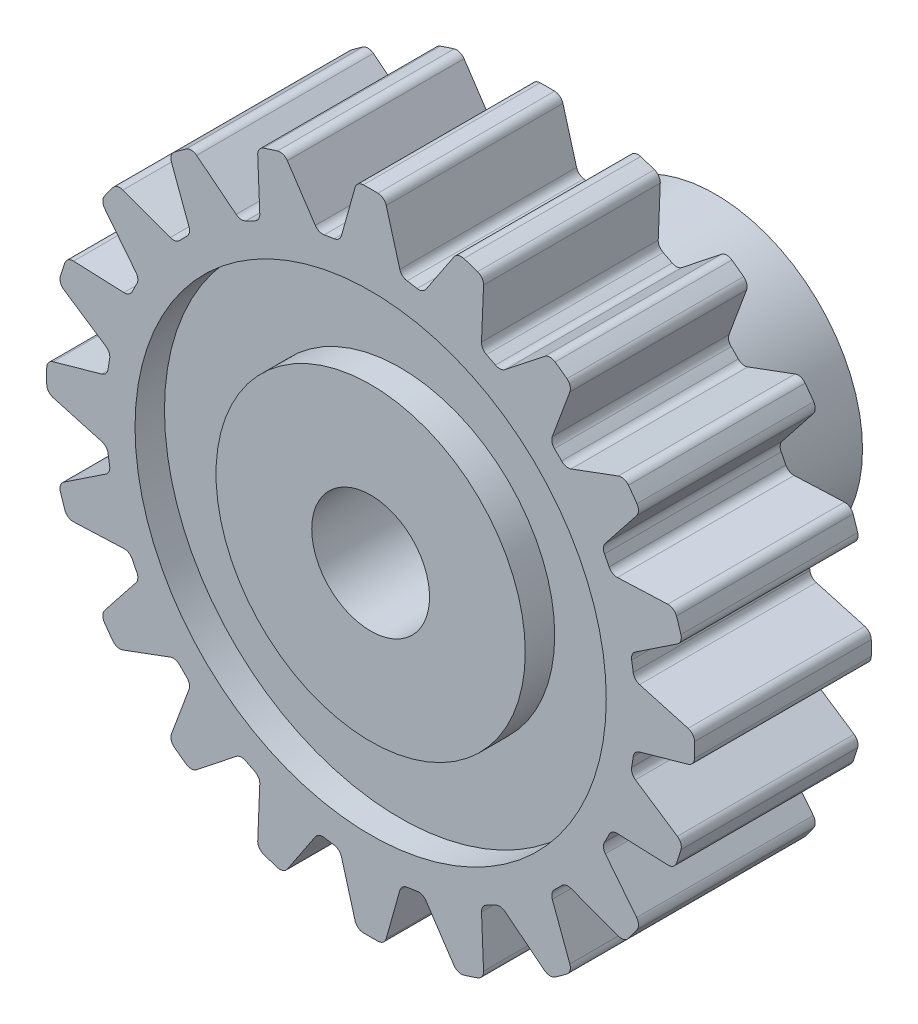
SolidWorks part; units mm, degrees
ref_plane "Front Plane" through (0, 0, 0) normal (0, 0, 1) x (1, 0, 0)
ref_plane "Top Plane" through (0, 0, 0) normal (0, 1, 0) x (1, 0, 0)
ref_plane "Right Plane" through (0, 0, 0) normal (1, 0, 0) x (0, 0, -1)
sketch "Sketch1" plane through (0, 0, 0) normal (0, 0, 1) x (1, 0, 0)
  circle A2 centre (0, 0) radius 9
  dimension "Blank diameter" = 18
extrude "Body" add sketch "Sketch1" against normal blind 6
sketch "Sketch2" plane through (0, 0, 0) normal (0, 0, 1) x (1, 0, 0)
  line L0 (0, 16.3446) -> (0, 3.6554) construction
  line L1 (-0.755, 9.9715) -> (-1.0446, 8.9392)
  line L2 (-0.755, 9.9715) -> (-0.4693, 10.99)
  line L3 (0.755, 9.9715) -> (1.0446, 8.9392)
  line L4 (0.755, 9.9715) -> (0.4693, 10.99)
  line L5 (0, 0) -> (-3.338, 44.0862) construction
  line L6 (0, 0) -> (3.224, 42.5807) construction
  arc A0 (0.4693, 10.99) -> (-0.4693, 10.99) centre (0, 0) ccw
  arc A1 (0.755, 9.9715) -> (-0.755, 9.9715) centre (0, 0) ccw construction
  arc A2 (1.0446, 8.9392) -> (-1.0446, 8.9392) centre (0, 0) ccw
  point P1 (0, 10)
  dimension "D2" = 20
  dimension "D3" = 20
  dimension "Full diameter" = 22
  dimension "Pitch diameter" = 20
  dimension "Blank diameter" = 18
  dimension "Tooth width PCD" = 1.51
extrude "Tooth" add sketch "Sketch2" against normal blind 6
fillet "Tooth Fillet" radius 0.3 4 edges at (-0.4693, 10.99, -3) (-1.0446, 8.9392, -3) (0.4693, 10.99, -3) (1.0446, 8.9392, -3)
pattern_circular "Tooth Pattern" count 20 over 360 about axis through (0, 0, 0) along (0, 0, 1) of "Tooth", "Tooth Fillet"
ref_axis "Axis1" through (0, 0, 0) along (0, 0, -1)
sketch "Sketch3" plane through (0, 0, 0) normal (0, 0, 1) x (1, 0, 0)
  circle A0 centre (0, 0) radius 5.25
  circle A1 centre (0, 0) radius 8
  dimension "Plastic boss" = 10.5
  dimension "Resses" = 16
extrude "Resses1" cut sketch "Sketch3" against normal blind 1
sketch "Sketch4" plane through (0, 0, -6) normal (0, 0, -1) x (-1, 0, 0)
  circle A0 centre (0, 0) radius 8
  circle A1 centre (0, 0) radius 5.25
  dimension "Plastic boss" = 10.5
  dimension "Resses" = 16
extrude "Resses2" cut sketch "Sketch4" against normal blind 1
sketch "Sketch5" plane through (0, 0, -6) normal (0, 0, -1) x (-1, 0, 0)
  circle A0 centre (0, 0) radius 5
  dimension "D1" = 10
extrude "Brass boss" add sketch "Sketch5" along normal blind 5.7
sketch "Sketch6" plane through (0, 0, -11.7) normal (0, 0, -1) x (-1, 0, 0)
  circle A0 centre (0, 0) radius 2
  dimension "D1" = 4
extrude "Bore" cut sketch "Sketch6" against normal through all
sketch "Sketch7" plane through (0, 0, 0) normal (0, 1, 0) x (1, 0, 0)
  circle A0 centre (0, 8.8626) radius 1
  dimension "D1" = 2
extrude "Grub screw" cut sketch "Sketch7" against normal through all
sketch "Sketch8" plane through (0, 0, -5) normal (0, 0, -1) x (-1, 0, 0)
  circle A0 centre (-0.8321, 10.5608) radius 1.8434
extrude "Extrude1" [suppressed] add sketch "Sketch8" along normal blind 5
